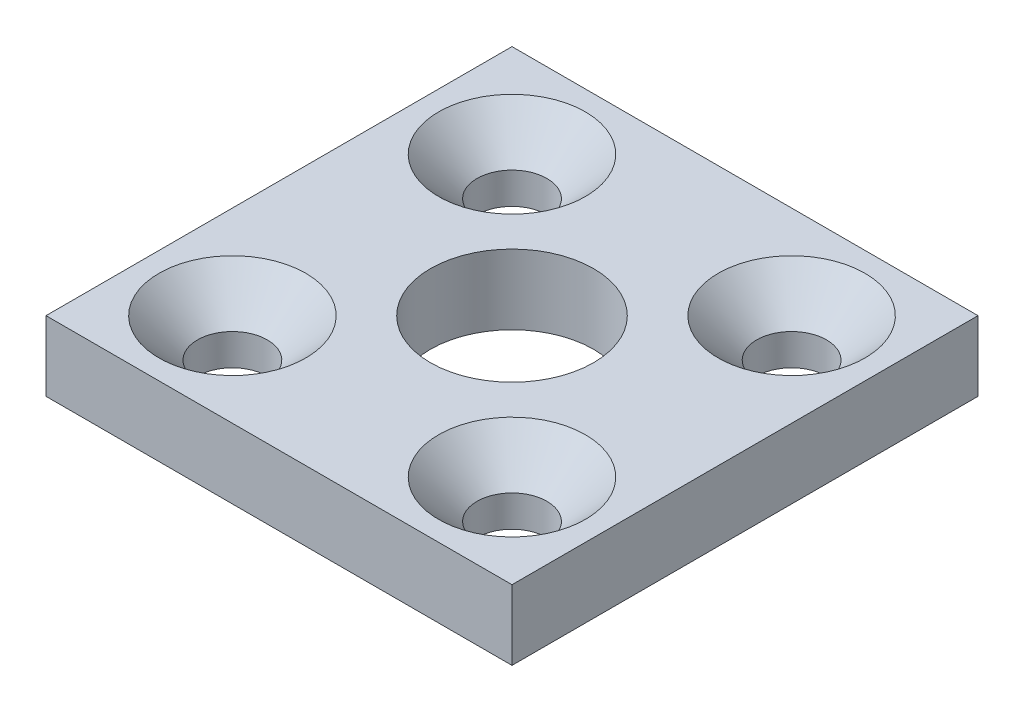
SolidWorks part; units mm, degrees
ref_plane "Front Plane" through (0, 0, 0) normal (0, 0, 1) x (1, 0, 0)
ref_plane "Top Plane" through (0, 0, 0) normal (0, 1, 0) x (1, 0, 0)
ref_plane "Right Plane" through (0, 0, 0) normal (1, 0, 0) x (0, 0, -1)
sketch "Sketch1" plane through (0, 0, 0) normal (0, 1, 0) x (1, 0, 0)
  line L0 (0, 10) -> (20, 10) construction
  line L1 (0, 0) -> (20, 0)
  line L2 (0, 0) -> (0, 20)
  line L3 (0, 20) -> (20, 20)
  line L4 (20, 0) -> (20, 20)
  line L5 (10, 20) -> (10, 0) construction
  line L6 (20, 20) -> (0, 0) construction
  circle A0 centre (16, 16) radius 1.5
  circle A1 centre (4, 16) radius 1.5
  circle A2 centre (16, 4) radius 1.5
  circle A3 centre (4, 4) radius 1.5
  circle A4 centre (10, 10) radius 3.5
  dimension "D2" = 3
  dimension "D4" = 7
  dimension "D1" = 20
  dimension "D3" = 4
extrude "Boss-Extrude1" add sketch "Sketch1" along normal blind 3
chamfer "Chamfer1" distance 1.65 angle 45 4 edges at (16, 3, -5.5) (4, 3, -2.5) (4, 3, -17.5) (16, 3, -14.5)
